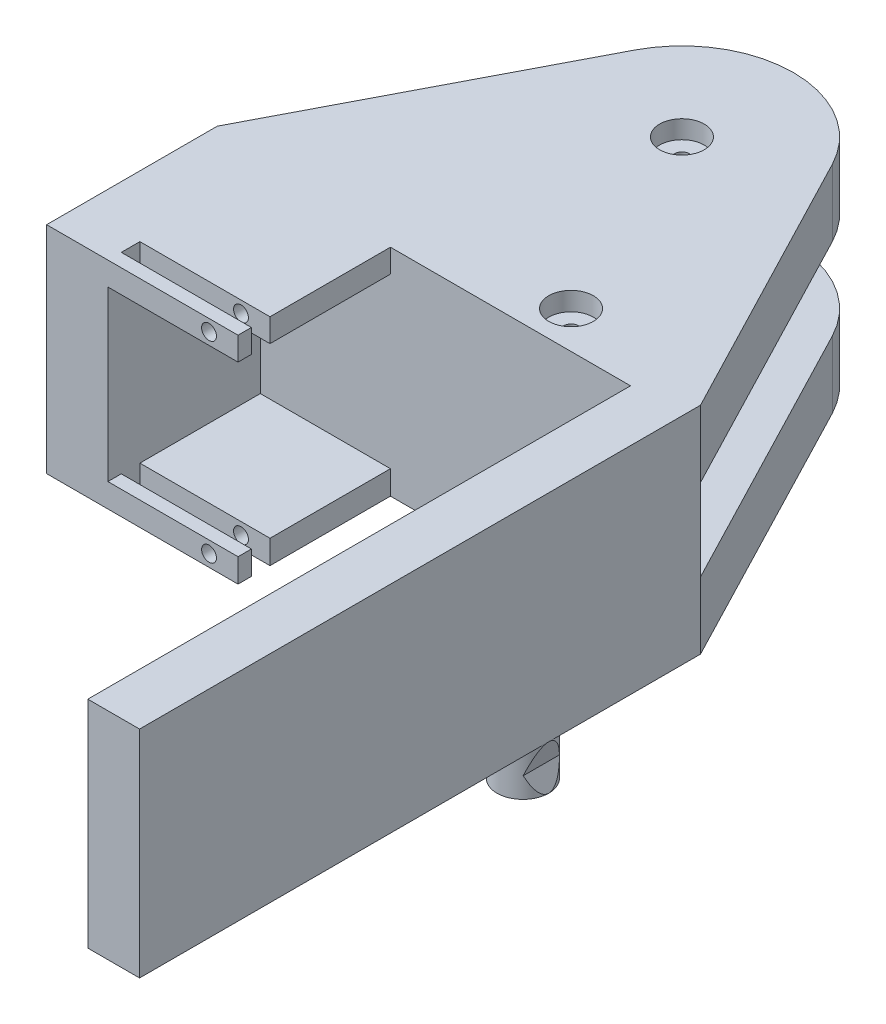
SolidWorks part; units mm, degrees
material "Copper"
ref_plane "Front Plane" through (0, 0, 0) normal (0, 0, 1) x (1, 0, 0)
ref_plane "Top Plane" through (0, 0, 0) normal (0, 1, 0) x (1, 0, 0)
ref_plane "Right Plane" through (0, 0, 0) normal (1, 0, 0) x (0, 0, -1)
sketch "Sketch1" plane through (0, 0, 0) normal (0, 0, 1) x (1, 0, 0)
  line L0 (0, 11) -> (65, 11)
  line L1 (0, 0) -> (65, 0)
  line L2 (0, 0) -> (0, 65)
  line L3 (0, 65) -> (65, 65)
  line L4 (65, 0) -> (65, 65)
  line L5 (0, 0) -> (65, 0)
  line L6 (0, 0) -> (0, 10)
  line L7 (0, 10) -> (65, 10)
  line L8 (65, 0) -> (65, 10)
  line L9 (0, 10) -> (65, 10)
  line L10 (0, 10) -> (0, 20)
  line L11 (0, 20) -> (65, 20)
  line L12 (65, 10) -> (65, 20)
  line L13 (65, 20) -> (0, 20)
  line L14 (65, 20) -> (65, 30)
  line L15 (65, 30) -> (0, 30)
  line L16 (0, 20) -> (0, 30)
  line L17 (0, 30) -> (65, 30)
  line L18 (0, 30) -> (0, 40)
  line L19 (0, 40) -> (65, 40)
  line L20 (65, 30) -> (65, 40)
  line L21 (0, 31) -> (65, 31)
  line L22 (36.97, 30) -> (36.97, 31) construction
  line L23 (37.8533, 10) -> (37.8533, 11) construction
  dimension "D1" = 65
  dimension "D2" = 65
  dimension "D3" = 10
  dimension "D4" = 1
extrude "Boss-Extrude1" add sketch "Sketch1" along normal blind 45 contours L11 L2 L7 L4 | L19 L2 L15 L4 region at (32.5, 15.5, 0) region at (32.5, 35.5, 0)
sketch "Sketch2" plane through (0, 10, 0) normal (0, -1, 0) x (1, 0, 0)
  line L0 (32.5, 0) -> (32.5, 45) construction
  line L3 (0, 45) -> (19.1907, 8.0816)
  line L4 (65, 45) -> (45.8093, 8.0816)
  line L5 (0, 45) -> (0, 0)
  line L6 (0, 0) -> (65, 0)
  line L7 (65, 0) -> (65, 45)
  circle A0 centre (32.5, 15) radius 15
  circle A1 centre (32.5, 15) radius 1
  point P2 (0, 0)
  point P3 (0, 0)
  point P4 (0, 0)
  dimension "D1" = 30
  dimension "D2" = 2
  dimension "D3" = 65
  dimension "D4" = 45
extrude "Cut-Extrude5" cut sketch "Sketch2" against normal blind 34 contours A0 L6 L4 | L0 A1 | A1 L0 | A1 region at (56.7767, 10, 14.6593) region at (32.0756, 10, 15) region at (32.9244, 10, 15)
extrude "Cut-Extrude6" cut sketch "Sketch2<6>" against normal blind 34 contours A0 L3 region at (8.2233, 10, 14.6593)
sketch "Sketch2<6>" plane through (0, 10, 0) normal (0, -1, 0) x (1, 0, 0) same geometry as "Sketch2"
sketch "Sketch3" plane through (0, 40, 0) normal (0, 1, 0) x (1, 0, 0)
  circle A0 centre (32.5, -15) radius 3
  dimension "D1" = 6
extrude "Cut-Extrude7" cut sketch "Sketch3" against normal blind 2.45
sketch "Sketch4" plane through (0, 20, 0) normal (0, 1, 0) x (1, 0, 0)
  circle A0 centre (32.5, -15) radius 3
extrude "Cut-Extrude8" cut sketch "Sketch4" against normal blind 2.45
sketch "Sketch5" plane through (0, 0, 45) normal (0, 0, 1) x (1, 0, 0)
  line L1 (0, 11) -> (65, 11)
  line L2 (0, 11) -> (0, 40)
  line L3 (0, 40) -> (65, 40)
  line L4 (65, 11) -> (65, 40)
extrude "Boss-Extrude2" add sketch "Sketch5" along normal blind 2.45
sketch "Sketch6" plane through (0, 11, 0) normal (0, -1, 0) x (1, 0, 0)
  line L0 (32.5, 15) -> (32.5, 26.7) construction
  line L1 (29, 26.7) -> (36, 26.7)
  line L2 (29, 26.7) -> (29, 33.5539)
  line L3 (29, 33.5539) -> (36, 33.5539)
  line L4 (36, 26.7) -> (36, 33.5539)
  line L5 (32.5, 26.7) -> (32.5, 28.3) construction
  circle A0 centre (32.5, 15) radius 11.5
  circle A1 centre (32.5, 28.3) radius 0.75
  dimension "D1" = 23
  dimension "D2" = 1.5
  dimension "D3" = 7
  dimension "D4" = 1.6
  dimension "D5" = 11.7
extrude "Boss-Extrude3" add sketch "Sketch6" along normal blind 3.35 contours L1 L4 L3 L2 region at (32.5, 11, 30.1968)
sketch "Sketch7" plane through (0, 7.65, 0) normal (0, -1, 0) x (1, 0, 0)
  line L0 (29, 29.7) -> (29, 26.7)
  line L1 (29, 26.7) -> (29, 33.5539) construction
  line L2 (29, 26.7) -> (36, 26.7) construction
  line L3 (29, 26.7) -> (31, 26.7)
  line L4 (31, 26.7) -> (29, 29.7)
  line L5 (34, 26.7) -> (36, 29.7)
  line L6 (36, 26.7) -> (36, 33.5539) construction
  line L7 (36, 29.7) -> (36, 26.7)
  line L8 (36, 26.7) -> (34, 26.7)
  dimension "D1" = 2
  dimension "D2" = 3
extrude "Cut-Extrude9" cut sketch "Sketch7" against normal blind 3.35
sketch "Sketch8" plane through (0, 7.65, 0) normal (0, -1, 0) x (1, 0, 0)
  line L0 (32.5, 33.5539) -> (32.5, 30.1922) construction
  line L1 (29, 33.5539) -> (36, 33.5539) construction
  line L2 (30.4549, 30.3333) -> (30.2789, 27.7817)
  line L3 (31, 26.7) -> (29, 29.7) construction
  line L4 (34.5451, 30.3333) -> (34.7211, 27.7817)
  line L5 (36, 29.7) -> (34, 26.7) construction
  line L7 (29.45, 30.2005) -> (29.4468, 29.0297)
  line L8 (35.55, 30.2005) -> (35.5532, 29.0297)
  line L9 (30.2789, 27.7817) -> (31, 26.7) construction
  line L10 (34.7211, 27.7817) -> (34, 26.7) construction
  line L11 (30.2789, 27.7817) -> (29.4468, 29.0297) construction
  line L12 (35.5532, 29.0297) -> (34.7211, 27.7817) construction
  circle A0 centre (32.5, 30.1922) radius 2.05
  circle A1 centre (32.5, 30.1922) radius 3.05
  line M1 (29, 29.7) -> (31, 26.7)
  line M3 (34, 26.7) -> (36, 29.7)
  line M4 (36, 29.7) -> (36, 33.5539)
  line M5 (36, 33.5539) -> (29, 33.5539)
  line M6 (29, 33.5539) -> (29, 29.7)
  dimension "D1" = 4.1
  dimension "D3" = 1
  dimension "D2" = 3.3617
  dimension "D4" = 1.3
  dimension "D5" = 1.5
extrude "Boss-Extrude4" add sketch "Sketch8" along normal blind 2 contours A1 L8 L7 M3 M4 M5 M6 M1 | L4 A1 L2 A0 | A1 L7 L2 M1 | A1 L4 L8 M3 region at (30.2975, 7.65, 29.2123) region at (29.7908, 7.65, 28.7274) region at (29.3651, 7.65, 29.6153) region at (35.2092, 7.65, 28.7274)
sketch "Sketch9" plane through (0, 0, 47.45) normal (0, 0, 1) x (1, 0, 0)
  line L0 (65, 40) -> (0, 40) construction
  line L1 (65, 11) -> (58.0376, 11)
  line L2 (65, 11) -> (65, 40)
  line L3 (65, 40) -> (58.0376, 40)
  line L4 (58.0376, 11) -> (58.0376, 40)
extrude "Boss-Extrude5" add sketch "Sketch9" along normal blind 73
sketch "Sketch10" plane through (0, 11, 0) normal (0, -1, 0) x (1, 0, 0)
  line L0 (45.0376, 42.45) -> (45.0376, 47.45) construction
  line L1 (0, 47.45) -> (58.0376, 47.45) construction
  line L2 (58.0376, 120.45) -> (58.0376, 47.45) construction
  circle A0 centre (45.0376, 42.45) radius 3
  dimension "D1" = 6
  dimension "D2" = 13
  dimension "D3" = 5
extrude "Cut-Extrude10" cut sketch "Sketch10" against normal blind 2.5
sketch "Sketch11" plane through (0, 40, 0) normal (0, 1, 0) x (1, 0, 0)
  line L0 (45.0376, -42.45) -> (45.0376, -47.45) construction
  line L1 (58.0376, -47.45) -> (0, -47.45) construction
  line L2 (58.0376, -120.45) -> (58.0376, -47.45) construction
  circle A0 centre (45.0376, -42.45) radius 3
  dimension "D1" = 6
  dimension "D2" = 5
  dimension "D3" = 13
extrude "Cut-Extrude11" cut sketch "Sketch11" against normal blind 2.5
sketch "Sketch12" plane through (0, 37.5, 0) normal (0, 1, 0) x (1, 0, 0)
  circle A0 centre (45.0376, -42.45) radius 1
extrude "Cut-Extrude12" cut sketch "Sketch12" against normal blind 32.5
sketch "Sketch13" plane through (0, 0, 47.45) normal (0, 0, 1) x (1, 0, 0)
  line L0 (0, 11) -> (58.0376, 11) construction
  line L1 (25.7437, 11) -> (0, 11)
  line L2 (25.7437, 11) -> (25.7437, 40)
  line L3 (25.7437, 40) -> (0, 40)
  line L4 (0, 11) -> (0, 40)
extrude "Boss-Extrude6" add sketch "Sketch13" along normal blind 20.5
sketch "Sketch14" plane through (25.7437, 0, 0) normal (1, 0, 0) x (0, 0, -1)
  line L0 (-47.45, 11) -> (-47.45, 40) construction
  line L1 (-47.45, 9.15) -> (-63.65, 9.15)
  line L2 (-47.45, 9.15) -> (-47.45, 41.85)
  line L3 (-47.45, 41.85) -> (-63.65, 41.85)
  line L4 (-63.65, 9.15) -> (-63.65, 41.85)
  line L5 (-63.65, 25.5) -> (-67.95, 25.5) construction
  line L6 (-67.95, 11) -> (-67.95, 40) construction
  dimension "D1" = 16.2
  dimension "D2" = 32.7
extrude "Cut-Extrude13" cut sketch "Sketch14" against normal blind 17.5
sketch "Sketch16" plane through (8.2437, 0, 0) normal (1, 0, 0) x (0, 0, -1)
  line L0 (-47.45, 11) -> (-47.45, 40) construction
  line L1 (-63.65, 11) -> (-47.45, 11)
  line L2 (-63.65, 11) -> (-63.65, 14.1979)
  line L3 (-63.65, 14.1979) -> (-47.45, 14.1979)
  line L4 (-47.45, 11) -> (-47.45, 14.1979)
  line L5 (-63.65, 40) -> (-47.45, 40)
  line L6 (-63.65, 40) -> (-63.65, 36.8625)
  line L7 (-63.65, 36.8625) -> (-47.45, 36.8625)
  line L8 (-47.45, 40) -> (-47.45, 36.8625)
extrude "Boss-Extrude7" add sketch "Sketch16" along normal blind 17.5
sketch "Sketch17" plane through (25.7437, 0, 0) normal (1, 0, 0) x (0, 0, -1)
  line L0 (-63.65, 36.8625) -> (-47.45, 36.8625) construction
  line L1 (-67.95, 11) -> (-66.15, 11)
  line L2 (-67.95, 11) -> (-67.95, 14.1979)
  line L3 (-67.95, 14.1979) -> (-66.15, 14.1979)
  line L4 (-66.15, 11) -> (-66.15, 14.1979)
  line L5 (-67.95, 40) -> (-66.15, 40)
  line L6 (-67.95, 40) -> (-67.95, 36.8625)
  line L7 (-67.95, 36.8625) -> (-66.15, 36.8625)
  line L8 (-66.15, 40) -> (-66.15, 36.8625)
  line L9 (-47.45, 14.1979) -> (-63.65, 14.1979) construction
  line L10 (-63.65, 14.1979) -> (-63.65, 36.8625) construction
  line L12 (-67.95, 36.8625) -> (-63.65, 36.8625)
  line L13 (-67.95, 36.8625) -> (-67.95, 14.1979)
  line L14 (-67.95, 14.1979) -> (-63.65, 14.1979)
  line L15 (-63.65, 36.8625) -> (-63.65, 14.1979)
  line L16 (-63.65, 14.1979) -> (-66.15, 14.1979)
  line L17 (-63.65, 14.1979) -> (-63.65, 11)
  line L18 (-63.65, 11) -> (-66.15, 11)
  line L19 (-66.15, 14.1979) -> (-66.15, 11)
  line L20 (-63.65, 36.8625) -> (-66.15, 36.8625)
  line L21 (-63.65, 36.8625) -> (-63.65, 40)
  line L22 (-63.65, 40) -> (-66.15, 40)
  line L23 (-66.15, 36.8625) -> (-66.15, 40)
  line M4 (-67.95, 11) -> (-47.45, 11)
  line M7 (-63.65, 14.1979) -> (-63.65, 36.8625)
  line M10 (-47.45, 40) -> (-67.95, 40)
  line M11 (-67.95, 40) -> (-67.95, 11)
  dimension "D1" = 2.5
extrude "Cut-Extrude14" cut sketch "Sketch17" against normal blind 17.5 contours L3 L14 L12 L7 M7 M11 | L17 L14 L4 M4 | L12 L21 L8 M10 region at (25.7437, 12.5989, 64.9) region at (25.7437, 25.5302, 65.8) region at (25.7437, 38.4312, 64.9)
sketch "Sketch19" plane through (0, 0, 67.95) normal (0, 0, 1) x (1, 0, 0)
  line L1 (8.2437, 36.8625) -> (8.2437, 14.1979) construction
  line L2 (21.8437, 38.4312) -> (25.7437, 38.4312) construction
  line L3 (25.7437, 36.8625) -> (25.7437, 40) construction
  line L4 (21.8437, 12.5989) -> (25.7437, 12.5989) construction
  line L5 (25.7437, 11) -> (25.7437, 14.1979) construction
  circle A0 centre (21.8437, 12.5989) radius 1
  circle A1 centre (21.8437, 38.4312) radius 1
  dimension "D1" = 2
  dimension "D2" = 12.6
  dimension "D3" = 12.6
extrude "Cut-Extrude15" cut sketch "Sketch19" against normal blind 10
sketch "Sketch20" plane through (0, 11, 0) normal (0, -1, 0) x (1, 0, 0)
  line L0 (65, 65.4111) -> (58.0376, 65.4111) construction
  line L1 (65, 120.45) -> (65, 45) construction
  line L2 (58.0376, 120.45) -> (58.0376, 47.45) construction
  circle A0 centre (61.5188, 65.4111) radius 3.4812
extrude "Boss-Extrude8" add sketch "Sketch20" along normal blind 6
sketch "Sketch22" plane through (0, 0, 120.45) normal (0, 0, 1) x (1, 0, 0)
  line L0 (65, 11) -> (65, 40) construction
  line L1 (65, 14.9198) -> (58.0376, 14.9198)
  line L2 (65, 14.9198) -> (65, 5)
  line L3 (65, 5) -> (58.0376, 5)
  line L4 (58.0376, 14.9198) -> (58.0376, 5)
  line L5 (58.0376, 40) -> (58.0376, 11) construction
  line L6 (58.0376, 5) -> (65, 5) construction
  line L7 (65, 5) -> (64, 7.7559)
  line L8 (64, 7.7559) -> (65, 11)
  line L9 (64, 7.7559) -> (65, 7.7559) construction
  dimension "D1" = 1
extrude "Cut-Extrude17" cut sketch "Sketch22" against normal blind 66 contours L8 L9 L2 | L9 L7 L2 region at (64.6667, 8.8372, 120.45) region at (64.6667, 6.8372, 120.45)
